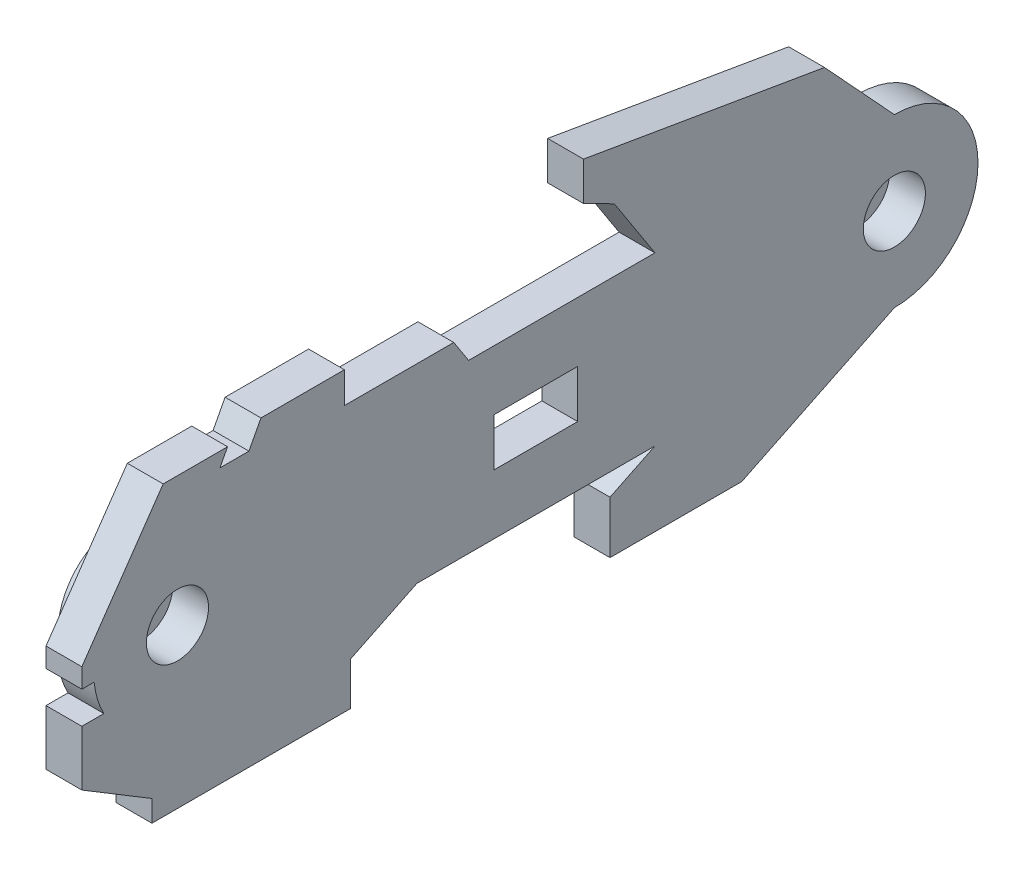
SolidWorks part; units mm, degrees
ref_plane "Front Plane" through (0, 0, 0) normal (0, 0, 1) x (1, 0, 0)
ref_plane "Top Plane" through (0, 0, 0) normal (0, 1, 0) x (1, 0, 0)
ref_plane "Right Plane" through (0, 0, 0) normal (1, 0, 0) x (0, 0, -1)
sketch "Sketch2" plane through (0, 0, 0) normal (0, 1, 0) x (1, 0, 0)
  line L0 (0, 0) -> (12, 0) construction
  line L1 (12, 30) -> (12, -30)
  line L2 (12, -30) -> (9, -30)
  line L3 (9, -30) -> (9, -1.5)
  line L4 (9, -1.5) -> (-9, -1.5)
  line L5 (0, 1.5) -> (0, -1.5) construction
  line L6 (-9, -30) -> (-9, -1.5)
  line L7 (-12, -30) -> (-9, -30)
  line L8 (-12, 30) -> (-12, -30)
  line L9 (-12, 30) -> (-9, 30)
  line L10 (-9, 30) -> (-9, 1.5)
  line L11 (9, 1.5) -> (-9, 1.5)
  line L12 (9, 30) -> (9, 1.5)
  line L13 (12, 30) -> (9, 30)
  point P13 (-12, 0)
  dimension "D1" = 3
  dimension "D2" = 3
  dimension "D3" = 30
extrude "Boss-Extrude1" add sketch "Sketch2" along normal blind 7 and the other way blind 7
sketch "Sketch3" plane through (12, 0, 0) normal (1, 0, 0) x (0, 0, -1)
  line L0 (-30, -7) -> (-30, 7) construction
  line L1 (30, -7) -> (30, 7) construction
  circle A0 centre (-30, 0) radius 7
  circle A1 centre (30, 0) radius 7
extrude "Boss-Extrude2" add sketch "Sketch3" against normal blind 3
ref_plane "Plane1" through (0, 0, 0) normal (-1, 0, 0) x (0, 0, 1)
mirror "Mirror1" about plane through (0, 0, 0) normal (-1, 0, 0) of "Boss-Extrude2"
sketch "Sketch4" plane through (0, 0, 0) normal (-1, 0, 0) x (0, 0, 1)
  circle A0 centre (-30, 0) radius 2.6
  circle A1 centre (30, 0) radius 2.6
  dimension "D1" = 5.2
  dimension "D2" = 5.2
extrude "Cut-Extrude1" cut sketch "Sketch4" against normal blind 23 and the other way blind 23
sketch "Sketch5" plane through (-12, 0, 0) normal (-1, 0, 0) x (0, 0, 1)
  line L0 (-30, 7) -> (-24.1554, 13.3392)
  line L4 (-6.564, 12.2529) -> (-9.9611, 7)
  line L5 (-30, 7) -> (30, 7) construction
  line L6 (5.6302, 7) -> (6.8729, 8.9217)
  line L7 (6.8729, 8.9217) -> (16.0243, 8.9217)
  line L8 (16.0243, 8.9217) -> (16.0243, 11.5202)
  line L9 (16.0243, 11.5202) -> (23.0108, 11.5202)
  line L10 (23.0108, 11.5202) -> (24.0174, 9.6146)
  line L11 (24.0174, 9.6146) -> (26.4427, 9.6146)
  line L12 (26.4427, 9.6146) -> (25.8021, 10.8273)
  line L13 (25.8021, 10.8273) -> (33.6254, 10.8273)
  line L14 (33.6254, 10.8273) -> (39.5845, 2.2088)
  line L15 (39.5845, 2.2088) -> (39.5845, -0.6496)
  line L16 (39.5845, -0.6496) -> (35.4504, -0.6496)
  line L17 (35.4504, -0.6496) -> (35.4504, 3.2482)
  line L18 (35.4504, 3.2482) -> (30.5617, 6.4097)
  line L19 (30.5617, 6.4097) -> (5.6302, 6.4097)
  line L20 (5.6302, 6.4097) -> (5.6302, 7)
  line L21 (-30, 7) -> (-9.9611, 7)
  line L22 (-30, -7) -> (-17.2297, -13.2151)
  line L23 (-17.2297, -13.2151) -> (-6.201, -13.2151)
  line L24 (-6.201, -13.2151) -> (-6.201, -8.83)
  line L25 (-6.201, -8.83) -> (-9.9611, -7)
  line L26 (-30, -7) -> (30, -7) construction
  line L27 (-9.9611, -7) -> (-30, -7)
  line L28 (9.9611, -7) -> (15.5248, -9.7078)
  line L29 (15.5248, -9.7078) -> (15.5248, -13.2959)
  line L30 (15.5248, -13.2959) -> (32.1353, -13.2959)
  line L31 (32.1353, -13.2959) -> (32.1353, -11.5018)
  line L32 (32.1353, -11.5018) -> (39.5845, -7)
  line L33 (39.5845, -7) -> (39.5845, -3.3348)
  line L34 (39.5845, -3.3348) -> (35.4504, -3.3348)
  line L35 (35.4504, -3.3348) -> (31.745, -5.5741)
  line L36 (31.745, -5.5741) -> (9.9611, -5.5741)
  line L37 (9.9611, -5.5741) -> (9.9611, -7)
  line L38 (-24.1554, 13.3392) -> (-3.9844, 16.7822)
  line L39 (-3.9844, 16.7822) -> (-3.9844, 13.5584)
  line L40 (-3.9844, 13.5584) -> (-6.564, 12.2529)
extrude "Boss-Extrude3" add sketch "Sketch5" against normal blind 3
mirror "Mirror2" about plane through (0, 0, 0) normal (-1, 0, 0) of "Boss-Extrude3"
sketch "Sketch6" plane through (0, 7, 0) normal (0, 1, 0) x (1, 0, 0)
  line L1 (-9, 37) -> (27.1461, 37)
  line L2 (-9, 37) -> (-9, -42.8814)
  line L3 (-9, -42.8814) -> (27.1461, -42.8814)
  line L4 (27.1461, 37) -> (27.1461, -42.8814)
extrude "Cut-Extrude2" cut sketch "Sketch6" against normal blind 30 and the other way blind 20
sketch "Sketch7" plane through (-9, 0, 0) normal (1, 0, 0) x (0, 0, -1)
  line L1 (-3, 1) -> (3, 1)
  line L2 (-3, 1) -> (-3, -1)
  line L3 (-3, -1) -> (3, -1)
  line L4 (3, 1) -> (3, -1)
  line L5 (-3, 1) -> (3, -1) construction
  line L6 (-3, -1) -> (3, 1) construction
  point P0 (0, 0)
extrude "Boss-Extrude4" add sketch "Sketch7" along normal blind 25
sketch "Sketch8" plane through (0, 1, 0) normal (0, 1, 0) x (1, 0, 0)
  line L0 (-9, 3) -> (-9, -3) construction
  line L1 (-9, -5.6302) -> (-9, 9.9611) construction
  circle A0 centre (13, 0) radius 1.5
  circle A1 centre (5, 0) radius 1.5
  dimension "D1" = 22
  dimension "D2" = 14
extrude "Cut-Extrude3" cut sketch "Sketch8" against normal blind 23
sketch "Sketch9" plane through (-9, 0, 0) normal (1, 0, 0) x (0, 0, -1)
  line L1 (-3, -1) -> (3, -1)
  line L2 (-3, -1) -> (-3, -3)
  line L3 (-3, -3) -> (3, -3)
  line L4 (3, -1) -> (3, -3)
  line L5 (-3, -1) -> (3, -1) construction
extrude "Boss-Extrude5" add sketch "Sketch9" along normal blind 11
sketch "Sketch10" plane through (-9, 0, 0) normal (1, 0, 0) x (0, 0, -1)
  line L1 (-48.6126, 20.8469) -> (-38, 20.8469)
  line L2 (-48.6126, 20.8469) -> (-48.6126, -22.2102)
  line L3 (-48.6126, -22.2102) -> (-38, -22.2102)
  line L4 (-38, 20.8469) -> (-38, -22.2102)
  dimension "D1" = 38
extrude "Cut-Extrude4" cut sketch "Sketch10" against normal blind 10
sketch "Sketch11" plane through (0, 0, 0) normal (-1, 0, 0) x (0, 0, 1)
  line L0 (39.9917, -1.8969) -> (29.1151, 13.8338)
  line L1 (29.1151, 13.8338) -> (39.9917, 13.8338)
  line L2 (39.9917, 13.8338) -> (39.9917, -1.8969)
  line L3 (38, 4.5003) -> (33.6254, 10.8273) construction
  dimension "D1" = 180
extrude "Cut-Extrude5" cut sketch "Sketch11" along normal blind 22
sketch "Sketch12" plane through (-12, 0, 0) normal (-1, 0, 0) x (0, 0, 1)
  line L0 (-29.2519, 5.4489) -> (-13.9, 4.4)
  line L1 (-29.2519, -5.4489) -> (-13.9, -4.4)
  line L2 (0, 0) -> (0, 24.3336) construction
  line L3 (29.2519, -5.4489) -> (13.9, -4.4)
  line L4 (29.2519, 5.4489) -> (13.9, 4.4)
  arc A2 (-29.2519, 5.4489) -> (-29.2519, -5.4489) centre (-30, 0) ccw
  arc A3 (-13.9, -4.4) -> (-13.9, 4.4) centre (-13.9, 0) ccw
  arc A4 (13.9, -4.4) -> (13.9, 4.4) centre (13.9, 0) cw
  arc A5 (29.2519, 5.4489) -> (29.2519, -5.4489) centre (30, 0) cw
  dimension "D1" = 13.9
  dimension "D2" = 8.8
extrude "Boss-Extrude6" add sketch "Sketch12" along normal blind 1.5
sketch "Sketch17" plane through (0, 1, 0) normal (0, 1, 0) x (1, 0, 0)
  line L1 (41, 9) -> (-9, 9)
  line L2 (41, 9) -> (41, -3)
  line L3 (41, -3) -> (-9, -3)
  line L4 (-9, 9) -> (-9, -3)
  line L5 (41, 9) -> (-9, -3) construction
  line L6 (41, -3) -> (-9, 9) construction
  point P0 (16, 3)
extrude "Cut-Extrude7" cut sketch "Sketch17" against normal blind 22
sketch "Sketch18" plane through (-9, 0, 0) normal (1, 0, 0) x (0, 0, -1)
  line L1 (-3.5, 2) -> (3.5, 2)
  line L2 (-3.5, 2) -> (-3.5, -2)
  line L3 (-3.5, -2) -> (3.5, -2)
  line L4 (3.5, 2) -> (3.5, -2)
  line L5 (-3.5, 2) -> (3.5, -2) construction
  line L6 (-3.5, -2) -> (3.5, 2) construction
  point P0 (0, 0)
  dimension "D1" = 4
  dimension "D2" = 7
extrude "Cut-Extrude8" cut sketch "Sketch18" against normal blind 22
